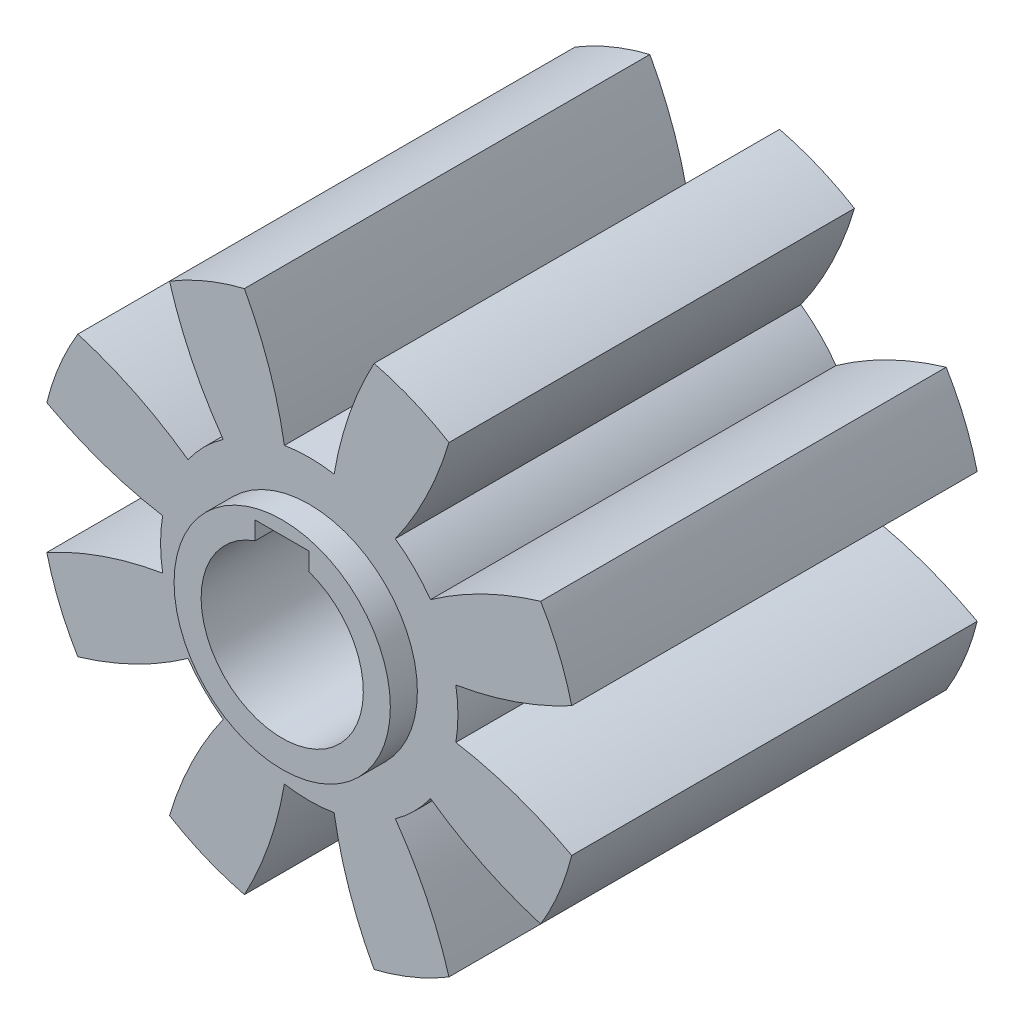
SolidWorks part; units mm, degrees
ref_plane "Front Plane" through (0, 0, 0) normal (0, 0, 1) x (1, 0, 0)
ref_plane "Top Plane" through (0, 0, 0) normal (0, 1, 0) x (1, 0, 0)
ref_plane "Right Plane" through (0, 0, 0) normal (1, 0, 0) x (0, 0, -1)
sketch "Sketch1" plane through (0, 0, 0) normal (0, 0, 1) x (1, 0, 0)
  circle A0 centre (0, 0) radius 10
  circle A1 centre (0, 0) radius 8 construction
  dimension "D1" = 16
  dimension "D2" = 20
extrude "Boss-Extrude1" add sketch "Sketch1" along normal mid plane 15
sketch "Sketch2" plane through (0, 0, 0) normal (0, 0, 1) x (1, 0, 0)
  line L0 (0, 0) -> (0, 10) construction
  line L1 (0, 0) -> (7.0711, 7.0711) construction
  line L2 (0, 0) -> (3.8268, 9.2388) construction
  line L3 (-0.9197, 5.4226) -> (0, 0) construction
  line L4 (-1.5607, 7.8463) -> (1.5607, 7.8463) construction
  line L5 (1.5607, 7.8463) -> (4.4446, 6.6518) construction
  line L6 (-2.2512, 9.7433) -> (0, 3.5582) construction
  circle A0 centre (0, 0) radius 10 construction
  circle A1 centre (0, 0) radius 14 construction
  arc A2 (0.9197, 5.4226) -> (-0.9197, 5.4226) centre (0, 0) ccw
  arc A3 (-2.3983, 9.7081) -> (-0.9197, 5.4226) centre (-14.5907, 3.1038) cw
  circle A4 centre (0, 0) radius 10 construction
  arc A5 (2.3983, 9.7081) -> (0.9197, 5.4226) centre (14.5907, 3.1038) ccw
  circle A6 centre (0, 0) radius 8 construction
  arc A7 (2.3983, 9.7081) -> (-2.3983, 9.7081) centre (0, 0) ccw
  point P9 (-0.9197, 5.4226)
  dimension "D1" = 45
  dimension "D2" = 4
  dimension "D3" = 4.5
  dimension "D4" = 20
extrude "Cut-Extrude1" cut sketch "Sketch2" against normal through all both and the other way through all
sketch "Sketch3" plane through (0, 0, 7.5) normal (0, 0, 1) x (1, 0, 0)
  line L1 (-1, 3.4951) -> (1, 3.4951)
  line L2 (-1, 3.4951) -> (-1, 2.1618)
  line L3 (-1, 2.1618) -> (1, 2.1618)
  line L4 (1, 3.4951) -> (1, 2.1618)
  circle A0 centre (0, 0) radius 4
  arc A1 (-1, 2.8284) -> (1, 2.8284) centre (0, 0) ccw
  point P8 (-1, 2.8284)
  point P9 (0, 2.1618)
  dimension "D1" = 8
  dimension "D2" = 6
  dimension "D3" = 2
  dimension "D4" = 1.3333
extrude "Boss-Extrude2" add sketch "Sketch3" along normal mid plane 2 contours A0 A1 L2 L1 L4 region at (-3.8869, 0, 7.5)
mirror "Mirror1" about plane through (0, 0, 0) normal (0, 0, 1) of "Boss-Extrude2"
extrude "Cut-Extrude2" cut sketch "Sketch3<3>" against normal through all both and the other way through all contours L2 A1 L4 L3 | L4 L1 L2 L3 region at (0, 2.8284, 7.5) region at (0, -0.1495, 7.5)
sketch "Sketch3<3>" plane through (0, 0, 7.5) normal (0, 0, 1) x (1, 0, 0) same geometry as "Sketch3"
pattern_circular "CirPattern2" count 8 over 360 about axis through (0, 0, 7.5) along (0, 0, 1) of "Cut-Extrude1"
equation "\"Module\"= 2mm"
equation "\"pressure angle\"= 20"
equation "\"num of teeth\"= 8"
equation "\"D1@Sketch1\"= \"Module\" * \"num of teeth\""
equation "\"D2@Sketch1\"= (\"num of teeth\" +2) * \"Module\""
equation "\"D1@Sketch2\"= 360 / \"num of teeth\""
equation "\"D2@Sketch2\"= \"Module\" * 2"
equation "\"D3@Sketch2\"=\"Module\" * if( \"Module\" => 1.25,2.25,2.4)"
equation "\"D4@Sketch2\"= \"pressure angle\""
equation "\"D3@Sketch3\"= 8 / 4"
equation "\"D1@CirPattern2\"= \"num of teeth\""
